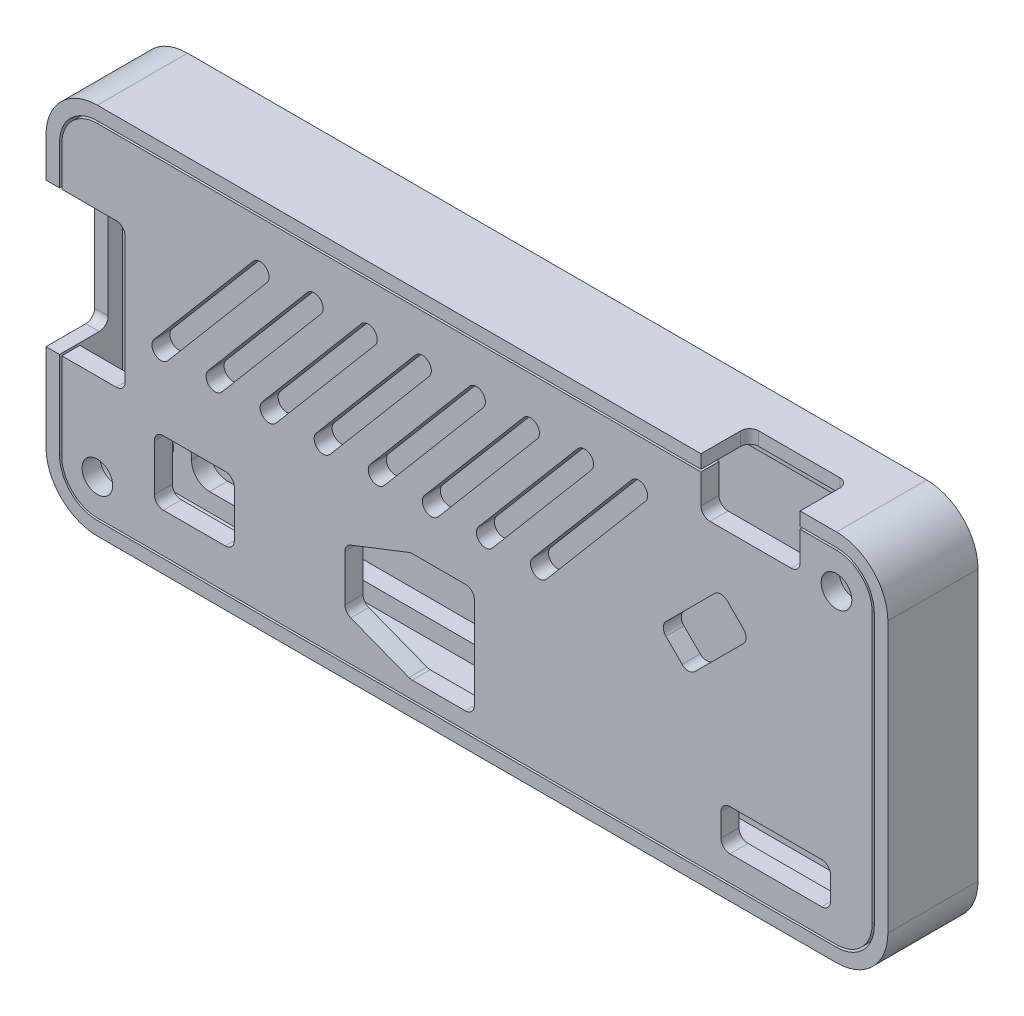
SolidWorks part; units mm, degrees
ref_plane "Front" through (0, 0, 0) normal (0, 0, 1) x (1, 0, 0)
ref_plane "Top" through (0, 0, 0) normal (0, 1, 0) x (1, 0, 0)
ref_plane "Right" through (0, 0, 0) normal (1, 0, 0) x (0, 0, -1)
sketch "Sketch1" plane through (0, 0, 0) normal (0, 0, 1) x (1, 0, 0)
  line L0 (-0.2, 4) -> (-0.2, 34)
  line L1 (4, 0) -> (86, 0) construction
  line L2 (0, 4) -> (0, 34) construction
  line L3 (4, 38) -> (86, 38) construction
  line L4 (90, 4) -> (90, 34) construction
  line L5 (4, 38.2) -> (86, 38.2)
  line L6 (90.2, 4) -> (90.2, 34)
  line L7 (4, -0.2) -> (86, -0.2)
  line L8 (4, 39.7) -> (86, 39.7)
  line L9 (91.7, 4) -> (91.7, 34)
  line L10 (4, -1.7) -> (86, -1.7)
  line L11 (-1.7, 4) -> (-1.7, 34)
  arc A0 (86, 38) -> (90, 34) centre (86, 34) cw construction
  arc A1 (86, 0) -> (90, 4) centre (86, 4) ccw construction
  arc A2 (4, 0) -> (0, 4) centre (4, 4) cw construction
  arc A3 (0, 34) -> (4, 38) centre (4, 34) cw construction
  arc A4 (-0.2, 34) -> (4, 38.2) centre (4, 34) cw
  arc A5 (86, 38.2) -> (90.2, 34) centre (86, 34) cw
  arc A6 (86, -0.2) -> (90.2, 4) centre (86, 4) ccw
  arc A7 (4, -0.2) -> (-0.2, 4) centre (4, 4) cw
  arc A8 (-1.7, 34) -> (4, 39.7) centre (4, 34) cw
  arc A9 (86, 39.7) -> (91.7, 34) centre (86, 34) cw
  arc A10 (86, -1.7) -> (91.7, 4) centre (86, 4) ccw
  arc A11 (4, -1.7) -> (-1.7, 4) centre (4, 4) cw
  point P9 (90, 0)
  point P12 (0, 0)
  point P15 (0, 38)
  dimension "D3" = 4
  dimension "D1" = 38
  dimension "D2" = 90
  dimension "D4" = 0.2
  dimension "D5" = 1.5
extrude "Boss-Extrude1" add sketch "Sketch1" against normal blind 3 contours L8 A9 L9 A10 L10 A11 L11 A8
extrude "Boss-Extrude2" add sketch "Sketch1<3>" along normal blind 7
sketch "Sketch1<3>" plane through (0, 0, 0) normal (0, 0, 1) x (1, 0, 0) same geometry as "Sketch1"
hole_wizard "M3x0.5 Tapped Hole1" positions "Sketch2" profile "Sketch3" tap size "M3x0.5" standard "ANSI Metric" end condition through all
sketch "Sketch2" plane through (0, 0, 0) normal (0, 0, 1) x (1, 0, 0)
  point P0 (4, 34)
  point P3 (4, 4)
  point P6 (86, 4)
  point P9 (86, 34)
sketch "Sketch3" plane through (4, 34, 0) normal (1, 0, 0) x (0, -1, 0)
  line L0 (0, 0) -> (0, 3)
  line L1 (0, 3) -> (1.45, 3)
  line L2 (1.45, 3) -> (1.45, 0)
  line L5 (1.45, 0) -> (0, 0)
  line L11 (0, -6.35) -> (0, 107.95) construction
  dimension "Thru Tap Drill Dia." = 2.9
  dimension "Thru Tap Drill Depth" = 3
cosmetic thread "Hole Thread1" parameters "D2"=3
cosmetic thread "Hole Thread2" parameters "D2"=3
cosmetic thread "Hole Thread3" parameters "D2"=3
cosmetic thread "Hole Thread4" parameters "D2"=3
sketch "Sketch4" plane through (0, 0, 0) normal (0, 0, 1) x (1, 0, 0)
  line L9 (1.8, 34) -> (1.8, 4)
  line L10 (86, 36.2) -> (4, 36.2)
  line L11 (88.2, 4) -> (88.2, 34)
  line L12 (4, 1.8) -> (86, 1.8)
  line L13 (1.8, 31.3425) -> (1.8, 6.6575)
  line L14 (83.3425, 36.2) -> (6.6575, 36.2)
  line L15 (88.2, 6.6575) -> (88.2, 31.3425)
  line L16 (6.6575, 1.8) -> (83.3425, 1.8)
  arc A6 (1.8, 31.3425) -> (6.6575, 36.2) centre (4, 34) ccw
  arc A15 (6.6575, 1.8) -> (1.8, 6.6575) centre (4, 4) ccw
  arc A16 (88.2, 6.6575) -> (83.3425, 1.8) centre (86, 4) ccw
  arc A17 (83.3425, 36.2) -> (88.2, 31.3425) centre (86, 34) ccw
  arc A26 (4, 36.2) -> (1.8, 34) centre (4, 34) ccw
  arc A27 (88.2, 34) -> (86, 36.2) centre (86, 34) ccw
  arc A28 (86, 1.8) -> (88.2, 4) centre (86, 4) ccw
  arc A29 (1.8, 4) -> (4, 1.8) centre (4, 4) ccw
  point P1 (86, 34)
  point P2 (4, 34)
  point P4 (4, 4)
  point P6 (86, 4)
  dimension "D1" = 3.45
  dimension "D6" = 2
extrude "Cut-Extrude1" cut sketch "Sketch4" against normal blind 2
fillet "Fillet1" radius 2 8 edges at (88.2, 31.3425, -1) (83.3425, 36.2, -1) (1.8, 31.3425, -1) (1.8, 6.6575, -1) (6.6575, 1.8, -1) (83.3425, 1.8, -1) (88.2, 6.6575, -1) (6.6575, 36.2, -1)
sketch "Sketch5" plane through (0, 0, 7) normal (0, 0, 1) x (1, 0, 0)
  line L1 (86, 37.95) -> (4, 37.95)
  line L2 (0.05, 34) -> (0.05, 4)
  line L3 (4, 0.05) -> (86, 0.05)
  line L4 (89.95, 4) -> (89.95, 34)
  line L5 (-0.2, 34) -> (-0.2, 4)
  line L6 (86, 38.2) -> (4, 38.2)
  line L7 (90.2, 4) -> (90.2, 34)
  line L8 (4, -0.2) -> (86, -0.2)
  line L9 (-0.2, 34) -> (-0.2, 4) construction
  line L10 (86, 38.2) -> (4, 38.2) construction
  line L11 (90.2, 4) -> (90.2, 34) construction
  line L12 (4, -0.2) -> (86, -0.2) construction
  arc A0 (4, 37.95) -> (0.05, 34) centre (4, 34) ccw
  arc A1 (0.05, 4) -> (4, 0.05) centre (4, 4) ccw
  arc A2 (86, 0.05) -> (89.95, 4) centre (86, 4) ccw
  arc A3 (89.95, 34) -> (86, 37.95) centre (86, 34) ccw
  arc A4 (-0.2, 4) -> (4, -0.2) centre (4, 4) ccw
  arc A5 (4, 38.2) -> (-0.2, 34) centre (4, 34) ccw
  arc A6 (90.2, 34) -> (86, 38.2) centre (86, 34) ccw
  arc A7 (86, -0.2) -> (90.2, 4) centre (86, 4) ccw
  arc A8 (-0.2, 4) -> (4, -0.2) centre (4, 4) ccw construction
  arc A9 (4, 38.2) -> (-0.2, 34) centre (4, 34) ccw construction
  arc A10 (90.2, 34) -> (86, 38.2) centre (86, 34) ccw construction
  arc A11 (86, -0.2) -> (90.2, 4) centre (86, 4) ccw construction
  dimension "D1" = 0
  dimension "D2" = 0.25
extrude "Boss-Extrude3" add sketch "Sketch5" against normal blind 2 separate body
sketch "Sketch6" plane through (0, 0, 7) normal (0, 0, 1) x (1, 0, 0)
  line L0 (38.7456, 14.0852) -> (31.4652, 11.2392) construction
  line L1 (45.8256, 14.0852) -> (38.7456, 14.0852) construction
  line L2 (45.8256, 1.9252) -> (45.8256, 14.0852) construction
  line L3 (38.7456, 1.9252) -> (45.8256, 1.9252) construction
  line L4 (31.4652, 4.7392) -> (38.7456, 1.9252) construction
  line L5 (31.4652, 11.2392) -> (31.4652, 4.7392) construction
  line L6 (-1.7, 29.6504) -> (7.082, 29.6504) construction
  line L7 (7.082, 13.6504) -> (-1.7, 13.6504) construction
  line L8 (7.082, 29.6504) -> (7.082, 13.6504) construction
  line L9 (19.1904, 11.6088) -> (19.1904, 4.4492) construction
  line L10 (10.3164, 11.6088) -> (10.3164, 4.4492) construction
  line L11 (10.3164, 4.4492) -> (19.1904, 4.4492) construction
  line L12 (10.3164, 11.6088) -> (19.1904, 11.6088) construction
  line L13 (81.967, 39.7) -> (81.967, 33.7) construction
  line L14 (70.967, 33.7) -> (81.967, 33.7) construction
  line L15 (70.967, 39.7) -> (70.967, 33.7) construction
  line L16 (69.5819, 17.7149) -> (66.3717, 20.9251) construction
  line L17 (66.3717, 20.9251) -> (73.1741, 27.7275) construction
  line L18 (73.1741, 27.7275) -> (76.3843, 24.5173) construction
  line L19 (76.3843, 24.5173) -> (69.5819, 17.7149) construction
  line L20 (73.188, 7.405) -> (73.188, 2.865) construction
  line L21 (73.188, 2.865) -> (85.348, 2.865) construction
  line L22 (85.348, 7.405) -> (85.348, 2.865) construction
  line L23 (73.188, 7.405) -> (85.348, 7.405) construction
  line L24 (38.7456, 14.0852) -> (31.4652, 11.2392)
  line L25 (45.8256, 14.0852) -> (38.7456, 14.0852)
  line L26 (45.8256, 1.9252) -> (45.8256, 14.0852)
  line L27 (38.7456, 1.9252) -> (45.8256, 1.9252)
  line L28 (31.4652, 4.7392) -> (38.7456, 1.9252)
  line L29 (31.4652, 11.2392) -> (31.4652, 4.7392)
  line L30 (-1.7, 29.6504) -> (7.082, 29.6504)
  line L31 (7.082, 13.6504) -> (-1.7, 13.6504)
  line L32 (7.082, 29.6504) -> (7.082, 13.6504)
  line L33 (19.1904, 11.6088) -> (19.1904, 4.4492)
  line L34 (10.3164, 11.6088) -> (10.3164, 4.4492)
  line L35 (10.3164, 4.4492) -> (19.1904, 4.4492)
  line L36 (10.3164, 11.6088) -> (19.1904, 11.6088)
  line L37 (81.967, 39.7) -> (81.967, 33.7)
  line L38 (70.967, 33.7) -> (81.967, 33.7)
  line L39 (70.967, 39.7) -> (70.967, 33.7)
  line L40 (69.5819, 17.7149) -> (66.3717, 20.9251)
  line L41 (66.3717, 20.9251) -> (73.1741, 27.7275)
  line L42 (73.1741, 27.7275) -> (76.3843, 24.5173)
  line L43 (76.3843, 24.5173) -> (69.5819, 17.7149)
  line L44 (73.188, 7.405) -> (73.188, 2.865)
  line L45 (73.188, 2.865) -> (85.348, 2.865)
  line L46 (85.348, 7.405) -> (85.348, 2.865)
  line L47 (73.188, 7.405) -> (85.348, 7.405)
  line L48 (-1.7, 29.6504) -> (-1.7, 13.6504)
  line L49 (70.967, 39.7) -> (81.967, 39.7)
extrude "Cut-Extrude2" cut sketch "Sketch6" against normal offset from surface (5.4 mm away) 1.6 up to face at (45, 19, 0)
fillet "Fillet2" radius 1 22 edges at (73.188, 2.865, 6) (85.348, 2.865, 6) (85.348, 7.405, 6) (73.188, 7.405, 6) (73.1741, 27.7275, 6) (66.3717, 20.9251, 6) (69.5819, 17.7149, 6) (76.3843, 24.5173, 6) (70.967, 33.7, 6) (81.967, 33.7, 6) (10.3164, 4.4492, 6) (19.1904, 4.4492, 6) (19.1904, 11.6088, 6) (10.3164, 11.6088, 6) (7.082, 13.6504, 6) (31.4652, 11.2392, 6) (31.4652, 4.7392, 6) (38.7456, 1.9252, 6) (45.8256, 1.9252, 6) (45.8256, 14.0852, 6) (38.7456, 14.0852, 6) (7.082, 29.6504, 6)
sketch "Sketch7" plane through (0, 0, 7) normal (0, 0, 1) x (1, 0, 0)
  line L0 (11.05, 19.7) -> (22.05, 32.7) construction
  line L1 (10.2866, 20.3459) -> (21.2866, 33.3459)
  line L2 (11.8134, 19.0541) -> (22.8134, 32.0541)
  line L3 (17.05, 19.7) -> (28.05, 32.7) construction
  line L4 (16.2866, 20.3459) -> (27.2866, 33.3459)
  line L5 (17.8134, 19.0541) -> (28.8134, 32.0541)
  line L6 (23.05, 19.7) -> (34.05, 32.7) construction
  line L7 (22.2866, 20.3459) -> (33.2866, 33.3459)
  line L8 (23.8134, 19.0541) -> (34.8134, 32.0541)
  line L9 (29.05, 19.7) -> (40.05, 32.7) construction
  line L10 (28.2866, 20.3459) -> (39.2866, 33.3459)
  line L11 (29.8134, 19.0541) -> (40.8134, 32.0541)
  line L12 (35.05, 19.7) -> (46.05, 32.7) construction
  line L13 (34.2866, 20.3459) -> (45.2866, 33.3459)
  line L14 (35.8134, 19.0541) -> (46.8134, 32.0541)
  line L15 (41.05, 19.7) -> (52.05, 32.7) construction
  line L16 (40.2866, 20.3459) -> (51.2866, 33.3459)
  line L17 (41.8134, 19.0541) -> (52.8134, 32.0541)
  line L18 (47.05, 19.7) -> (58.05, 32.7) construction
  line L19 (46.2866, 20.3459) -> (57.2866, 33.3459)
  line L20 (47.8134, 19.0541) -> (58.8134, 32.0541)
  line L21 (53.05, 19.7) -> (64.05, 32.7) construction
  line L22 (52.2866, 20.3459) -> (63.2866, 33.3459)
  line L23 (53.8134, 19.0541) -> (64.8134, 32.0541)
  line L24 (4, 39.7) -> (86, 39.7) construction
  arc A0 (10.2866, 20.3459) -> (11.8134, 19.0541) centre (11.05, 19.7) ccw
  arc A1 (22.8134, 32.0541) -> (21.2866, 33.3459) centre (22.05, 32.7) ccw
  arc A2 (16.2866, 20.3459) -> (17.8134, 19.0541) centre (17.05, 19.7) ccw
  arc A3 (28.8134, 32.0541) -> (27.2866, 33.3459) centre (28.05, 32.7) ccw
  arc A4 (22.2866, 20.3459) -> (23.8134, 19.0541) centre (23.05, 19.7) ccw
  arc A5 (34.8134, 32.0541) -> (33.2866, 33.3459) centre (34.05, 32.7) ccw
  arc A6 (28.2866, 20.3459) -> (29.8134, 19.0541) centre (29.05, 19.7) ccw
  arc A7 (40.8134, 32.0541) -> (39.2866, 33.3459) centre (40.05, 32.7) ccw
  arc A8 (34.2866, 20.3459) -> (35.8134, 19.0541) centre (35.05, 19.7) ccw
  arc A9 (46.8134, 32.0541) -> (45.2866, 33.3459) centre (46.05, 32.7) ccw
  arc A10 (40.2866, 20.3459) -> (41.8134, 19.0541) centre (41.05, 19.7) ccw
  arc A11 (52.8134, 32.0541) -> (51.2866, 33.3459) centre (52.05, 32.7) ccw
  arc A12 (46.2866, 20.3459) -> (47.8134, 19.0541) centre (47.05, 19.7) ccw
  arc A13 (58.8134, 32.0541) -> (57.2866, 33.3459) centre (58.05, 32.7) ccw
  arc A14 (52.2866, 20.3459) -> (53.8134, 19.0541) centre (53.05, 19.7) ccw
  arc A15 (64.8134, 32.0541) -> (63.2866, 33.3459) centre (64.05, 32.7) ccw
  point P2 (16.55, 26.2)
  point P7 (0, 0)
  point P10 (22.55, 26.2)
  point P17 (28.55, 26.2)
  point P24 (34.55, 26.2)
  point P31 (40.55, 26.2)
  point P38 (46.55, 26.2)
  point P45 (52.55, 26.2)
  point P52 (58.55, 26.2)
  dimension "D1" = 8
  dimension "D2" = 2
  dimension "D3" = 13
  dimension "D4" = 11
  dimension "D5" = 11
  dimension "D6" = 7
  dimension "D7" = 6
extrude "Cut-Extrude3" cut sketch "Sketch7" against normal up to surface (2 mm away) up to face at (38.6305, 8.0001, 5)
sketch "Sketch8" plane through (0, 0, 7) normal (0, 0, 1) x (1, 0, 0)
  circle A0 centre (4, 4) radius 1.7
  circle A1 centre (86, 34) radius 1.7
  dimension "D1" = 3.4
  dimension "D2" = 3.4
extrude "Cut-Extrude4" cut sketch "Sketch8" against normal through all
fillet "Fillet3" radius 1 4 edges at (70.967, 38.95, 1.6) (81.967, 38.95, 1.6) (-0.95, 13.6504, 1.6) (-0.95, 29.6504, 1.6)
